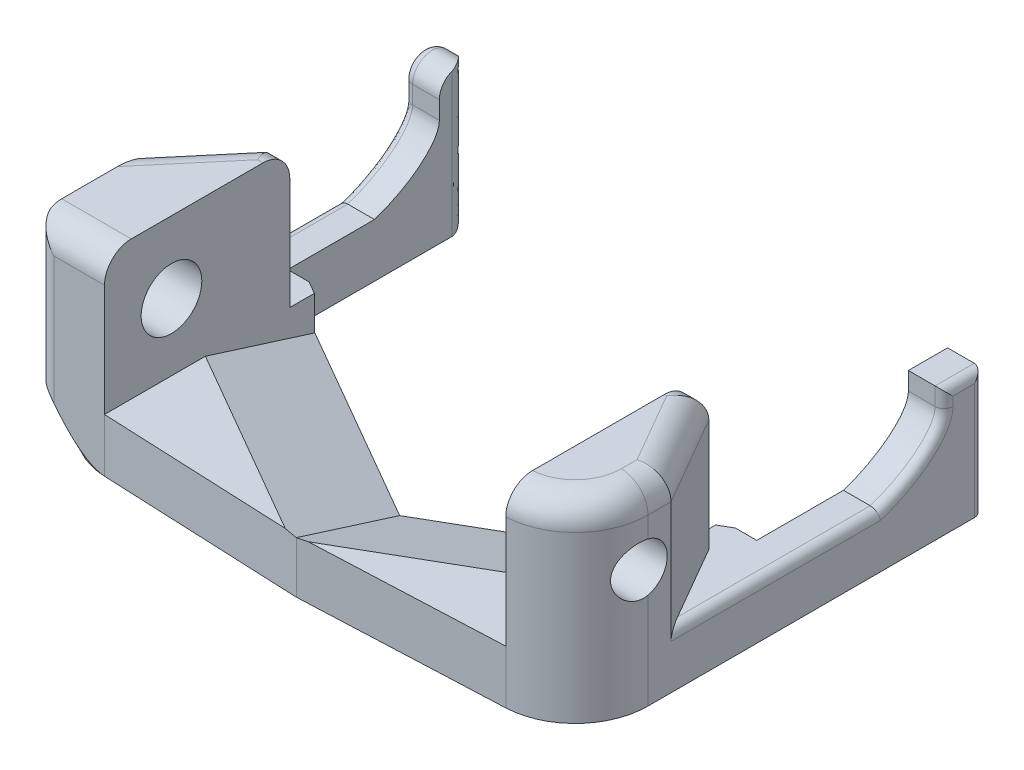
SolidWorks part; units mm, degrees
ref_plane "Front Plane" through (0, 0, 0) normal (0, 0, 1) x (1, 0, 0)
ref_plane "Top Plane" through (0, 0, 0) normal (0, 1, 0) x (1, 0, 0)
ref_plane "Right Plane" through (0, 0, 0) normal (1, 0, 0) x (0, 0, -1)
sketch "Sketch1" plane through (0, 0, 0) normal (0, 1, 0) x (1, 0, 0)
  line L0 (0, 0) -> (0, -6) construction
  line L1 (-11.8978, 6.8692) -> (0, 0) construction
  line L2 (0, 0) -> (11.25, 6.4952) construction
  line L3 (-11.25, -5.5048) -> (0, -6)
  line L4 (-11.8978, 6.8692) -> (-12.95, 6.8692) construction
  line L5 (-12.95, 14.8692) -> (-15.95, 14.8692) construction
  line L6 (-12.95, 6.8692) -> (-12.95, 14.8692) construction
  line L7 (-12.95, 14.8692) -> (-12.95, 17.3692) construction
  line L8 (0, 0) -> (-11.25, 6.4952) construction
  line L9 (-13.15, 14.8692) -> (-13.15, 17.3692)
  line L10 (-13.15, 6.6692) -> (-13.15, 14.8692)
  line L11 (-11.9514, 6.6692) -> (-13.15, 6.6692)
  line L12 (-11.9514, 6.6692) -> (0, -0.2309)
  line L13 (-11.9514, 6.6692) -> (-0.1, -0.1732) construction
  line L14 (-13.15, 17.3692) -> (-15.15, 17.3692)
  line L15 (-15.15, 17.3692) -> (-15.15, -1.4294)
  line L17 (11.9514, 6.6692) -> (0, -0.2309)
  line L18 (11.9514, 6.6692) -> (13.15, 6.6692)
  line L19 (13.15, 6.6692) -> (13.15, 14.8692)
  line L20 (13.15, 14.8692) -> (13.15, 17.3692)
  line L21 (13.15, 17.3692) -> (15.15, 17.3692)
  line L22 (15.15, 17.3692) -> (15.15, -1.4294)
  line L23 (11.25, -5.5048) -> (0, -6)
  arc A0 (-15.15, -1.4294) -> (-11.25, -5.5048) centre (-11.0706, -1.4294) ccw
  arc A1 (15.15, -1.4294) -> (11.25, -5.5048) centre (11.0706, -1.4294) cw
  dimension "D1" = 2.5
  dimension "D3" = 2
  dimension "D2" = 0.2
extrude "Boss-Extrude1" add sketch "Sketch1" against normal blind 1 contours L15 A0 L3 L23 A1 L22 L21 L20 L19 L18 L17 L12 L11 L10 L9 L14
sketch "Sketch2" plane through (0, 0, 0) normal (0, 1, 0) x (1, 0, 0)
  line L0 (-11.25, 6.2643) -> (-11.25, 0.1502)
  line L1 (-11.9514, 6.6692) -> (0, -0.2309) construction
  line L4 (-0.6469, -5.9715) -> (0, -6)
  line L11 (0, -0.2309) -> (-11.25, 6.2643)
  line L13 (-11.25, 6.4952) -> (-11.25, 0.1502) construction
  line L15 (0, -0.2309) -> (0, -6)
  line L17 (-0.6469, -5.9715) -> (-11.25, 0.1502)
sketch "Sketch3" plane through (0, 0, 0) normal (-0.171, -0.9397, 0.2962) x (0.9853, -0.1631, 0.0514)
  line L0 (0, 6.291) -> (-0.6566, 6.2965)
  line L1 (-0.6566, 6.2965) -> (-11.4182, 0.458)
  line L2 (-11.4182, 0.458) -> (-11.4182, -5.9809)
  line L3 (-11.4182, -6.1947) -> (-11.4182, 0.458) construction
  line L4 (-11.4182, -5.9809) -> (0, 0.2138)
  line L5 (0, 6.291) -> (0, 0) construction
  line L6 (0, 0.2138) -> (0, 6.291)
  line L7 (-12.1182, -6.3607) -> (0.0119, 0.2203) construction
loft "Loft1" add profiles "Sketch2", "Sketch3"
sketch "Sketch4" plane through (0, 0, 0) normal (0, 1, 0) x (1, 0, 0)
  line L0 (0, -0.2309) -> (0, -6)
  line L1 (0, -6) -> (0.6469, -5.9715)
  line L2 (11.25, -5.5048) -> (0, -6) construction
  line L3 (0.6469, -5.9715) -> (11.25, 0.1502)
  line L4 (11.25, 0.1502) -> (11.25, 6.2643)
  line L5 (11.9514, 6.6692) -> (0, -0.2309) construction
  line L6 (11.25, 6.2643) -> (0, -0.2309)
  line L7 (11.25, 0.1502) -> (11.25, 6.4952) construction
  line L8 (0.6469, -5.9715) -> (11.25, 0.1502) construction
sketch "Sketch5" plane through (0, 0, 0) normal (0.171, -0.9397, 0.2962) x (0.9853, 0.1631, -0.0514)
  line L0 (0, 0.2138) -> (0, 6.291)
  line L1 (0, 6.291) -> (0.6566, 6.2965)
  line L2 (0.6566, 6.2965) -> (11.4182, 0.458)
  line L4 (11.4182, 0.458) -> (11.4182, -5.9809)
  line L5 (11.4182, 0.458) -> (11.4182, -6.1947) construction
  line L6 (11.4182, -5.9809) -> (0, 0.2138)
  line L8 (11.4063, -5.9745) -> (-0.0119, 0.2203) construction
loft "Loft2" add profiles "Sketch4", "Sketch5"
sketch "Sketch6" plane through (0, 0, 0) normal (0, 1, 0) x (1, 0, 0)
  line L0 (-0.6469, -5.9715) -> (-11.25, 0.1502)
  line L1 (-11.25, 0.1502) -> (-11.25, -5.5048)
  line L2 (-11.25, -5.5048) -> (-0.6469, -5.9715)
sketch "Sketch7" plane through (0, 2, 0) normal (0, -1, 0) x (1, 0, 0)
  line L0 (-0.6469, 5.9715) -> (-11.25, 5.5048)
  line L1 (-11.25, 5.5048) -> (-11.25, -0.1502)
  line L2 (-11.25, -0.1502) -> (-0.6469, 5.9715)
loft "Loft3" add profiles "Sketch6", "Sketch7"
sketch "Sketch8" plane through (0, 0, 0) normal (0, 1, 0) x (1, 0, 0)
  line L0 (0.6469, -5.9715) -> (11.25, -5.5048)
  line L1 (11.25, -5.5048) -> (11.25, 0.1502)
  line L2 (11.25, 0.1502) -> (0.6469, -5.9715)
  point P7 (0.6469, -5.9616)
sketch "Sketch9" plane through (0, 2, 0) normal (0, -1, 0) x (1, 0, 0)
  line L0 (0.6469, 5.9715) -> (11.25, 5.5048)
  line L1 (11.25, 5.5048) -> (11.25, -0.1502)
  line L2 (11.25, -0.1502) -> (0.6469, 5.9715)
loft "Loft4" add profiles "Sketch8", "Sketch9"
sketch "Sketch11" plane through (0, 0, 0) normal (0, 1, 0) x (1, 0, 0)
  line L0 (11.25, 6.2643) -> (11.9514, 6.6692)
  line L1 (11.9514, 6.6692) -> (13.15, 6.6692)
  line L2 (13.15, 6.6692) -> (13.15, 17.3692)
  line L3 (13.15, 17.3692) -> (15.15, 17.3692)
  line L4 (15.15, 17.3692) -> (15.15, -1.4294)
  line L5 (11.25, 6.2643) -> (11.25, -5.5048)
  line L6 (0, -0.2039) -> (0, -6) construction
  line L7 (-11.25, 6.2643) -> (-11.25, -5.5048)
  line L8 (-15.15, 17.3692) -> (-15.15, -1.4294)
  line L9 (-13.15, 17.3692) -> (-15.15, 17.3692)
  line L10 (-13.15, 6.6692) -> (-13.15, 17.3692)
  line L11 (-11.9514, 6.6692) -> (-13.15, 6.6692)
  line L12 (-11.25, 6.2643) -> (-11.9514, 6.6692)
  arc A0 (15.15, -1.4294) -> (11.25, -5.5048) centre (11.0706, -1.4294) cw
  arc A1 (-15.15, -1.4294) -> (-11.25, -5.5048) centre (-11.0706, -1.4294) ccw
extrude "Boss-Extrude2" add sketch "Sketch11" along normal up to surface (2 mm away)
sketch "Sketch12" plane through (0, 2, 0) normal (0, 1, 0) x (1, 0, 0)
  line L0 (11.25, 4.8835) -> (12.25, 4.8835)
  line L1 (11.25, 0.1502) -> (11.25, 6.2643) construction
  line L2 (12.25, 4.8835) -> (15.15, -0.1394)
  line L3 (15.15, 17.3692) -> (15.15, -1.4294) construction
  line L4 (15.15, -0.1394) -> (15.15, -1.4294)
  line L5 (11.25, -5.5048) -> (11.25, 4.8835)
  line L6 (12.25, 4.8835) -> (12.5098, 5.0335) construction
  line L7 (12.8769, 4.3978) -> (11.45, 6.8692) construction
  line L8 (0, -0.2039) -> (0, -6) construction
  line L9 (-11.25, -5.5048) -> (-11.25, 4.8835)
  line L10 (-15.15, 1.45) -> (-15.15, -4.45)
  line L11 (-12.25, 4.8835) -> (-15.15, 1.45)
  line L12 (-11.25, 4.8835) -> (-12.25, 4.8835)
  line L13 (-15.15, -1.4294) -> (-15.15, 17.3692) construction
  line L14 (-11.25, -5.5048) -> (-14.0952, -5.5048)
  arc A0 (15.15, -1.4294) -> (11.25, -5.5048) centre (11.0706, -1.4294) cw
  arc A2 (-14.0952, -5.5048) -> (-15.15, -4.45) centre (-14.0952, -4.45) cw
  point P18 (-15.15, -4.4098)
  point P28 (-11.3233, -5.5009)
  dimension "D1" = 0.3
  dimension "D2" = 1
  dimension "D3" = 1.5
  dimension "D4" = 1
extrude "Boss-Extrude3" add sketch "Sketch12" along normal up to vertex (7.7765 mm away)
chamfer "Chamfer1" distance 3 angle 25 1 edges
sketch "Sketch15" plane through (-15.15, 0, 0) normal (-1, 0, 0) x (0, 0, 1)
  line L0 (-17.3692, 2) -> (-17.3692, 6)
  line L3 (-1.45, 2) -> (-17.3692, 2) construction
  line L4 (-15.1692, 5) -> (-15.1692, 13.2118)
  line L5 (-15.1692, 5) -> (-15.1692, 6)
  line L6 (-17.3692, 2) -> (-11.5321, 2)
  arc A0 (-17.3692, 6) -> (-15.1692, 6) centre (-16.2692, 6) cw
  spline S2 degree 3 poles (367.2976, 3980.0467) (-159.92, 375.1746) (23.9992, -4.3371) (-10.7642, 1.7947) (-11.0289, 1.8514) (-11.3061, 1.9293) (-11.4524, 1.9747) (-11.4629, 1.978) (-11.7199, 2.0588) (-12.1972, 2.2345) (-12.6635, 2.4564) (-12.9013, 2.5824) (-12.9151, 2.5898) (-13.1857, 2.7351) (-13.5424, 2.9502) (-13.9603, 3.2532) (-14.1499, 3.409) (-14.2436, 3.4911) (-14.2482, 3.4951) (-14.37, 3.6026) (-14.5274, 3.7548) (-14.7051, 3.9563) (-14.7832, 4.0563) (-14.8212, 4.1082) (-14.8226, 4.1101) (-14.9324, 4.2614) (-15.0167, 4.4063) (-19.4044, 15.2832) (110.5058, 42.3697) (3883.0831, -886.2187) knots -16.105172 -16.105172 -16.105172 -16.105172 0.125 0.125 0.1875 0.246094 0.246094 0.25 0.25 0.375 0.492187 0.492187 0.5 0.5 0.625 0.6875 0.746094 0.746094 0.75 0.75 0.8125 0.84375 0.873047 0.873047 0.875 0.875 0.9375 0.9375 5.506982 5.506982 5.506982 5.506982 only from (-9.8692, 1.7) to (-15.1692, 5)
  spline S3 degree 3 poles (-11.5321, 2) (-11.7604, 2.0738) (-12.217, 2.2439) (-12.6635, 2.4564) (-12.9013, 2.5824) (-12.9151, 2.5898) (-13.1857, 2.7351) (-13.5424, 2.9502) (-13.9603, 3.2532) (-14.1499, 3.409) (-14.2436, 3.4911) (-14.2482, 3.4951) (-14.37, 3.6026) (-14.5274, 3.7548) (-14.7051, 3.9563) (-14.7832, 4.0563) (-14.8212, 4.1082) (-14.8226, 4.1101) (-14.9324, 4.2614) (-15.0167, 4.4063) (-15.1351, 4.6998) (-15.1692, 4.8496) (-15.1692, 5) knots 0.26028 0.26028 0.26028 0.26028 0.375 0.492187 0.492187 0.5 0.5 0.625 0.6875 0.746094 0.746094 0.75 0.75 0.8125 0.84375 0.873047 0.873047 0.875 0.875 0.9375 0.9375 1 1 1 1
  dimension "D2" = 1
extrude "Boss-Extrude4" add sketch "Sketch15" against normal up to surface (2 mm away) up to face at (-13.15, 0.5, -12.0192)
sketch "Sketch16" plane through (15.15, 0, 0.3971) normal (-1, 0, 0) x (0, 0, 1)
  line L0 (-17.7662, 2) -> (-17.7662, 6)
  line L2 (-17.7662, 6) -> (-15.5662, 6)
  line L4 (-15.5662, 7.0453) -> (-15.5662, 5)
  line L6 (-17.7662, 2) -> (-11.9292, 2)
  line L7 (-15.5662, 6) -> (-15.5662, 5)
  spline S2 degree 3 poles (3882.6009, -887.4233) (110.1077, 42.3623) (-19.7973, 15.2821) (-15.4436, 4.4801) (-15.4077, 4.4073) (-15.3347, 4.2799) (-15.2915, 4.2116) (-15.2433, 4.143) (-15.2302, 4.1247) (-15.226, 4.1188) (-15.1484, 4.0118) (-14.9993, 3.8323) (-14.8011, 3.6357) (-14.6966, 3.5408) (-14.6683, 3.5155) (-14.6599, 3.508) (-14.4675, 3.338) (-14.1107, 3.0622) (-13.6578, 2.7806) (-13.4238, 2.6503) (-13.3606, 2.6158) (-13.3437, 2.6067) (-13.0913, 2.4711) (-12.6178, 2.244) (-12.1329, 2.0646) (-11.8838, 1.9855) (-11.8774, 1.9835) (29.4039, -10.9957) (-199.0711, 413.6868) (932.8156, 3879.3805) knots -4.510691 -4.510691 -4.510691 -4.510691 0.0625 0.0625 0.09375 0.09375 0.117188 0.123047 0.123047 0.125 0.125 0.1875 0.234375 0.246094 0.246094 0.25 0.25 0.375 0.46875 0.492188 0.492188 0.5 0.5 0.625 0.746094 0.746094 0.75 0.75 18.327221 18.327221 18.327221 18.327221 only from (-15.5662, 5) to (-10.2662, 1.7)
  spline S3 degree 3 poles (-15.5662, 5) (-15.5662, 4.8498) (-15.5322, 4.7001) (-15.4436, 4.4801) (-15.4077, 4.4073) (-15.3347, 4.2799) (-15.2915, 4.2116) (-15.2433, 4.143) (-15.2302, 4.1247) (-15.226, 4.1188) (-15.1484, 4.0118) (-14.9993, 3.8323) (-14.8011, 3.6357) (-14.6966, 3.5408) (-14.6683, 3.5155) (-14.6599, 3.508) (-14.4675, 3.338) (-14.1107, 3.0622) (-13.6578, 2.7806) (-13.4238, 2.6503) (-13.3606, 2.6158) (-13.3437, 2.6067) (-13.0913, 2.4711) (-12.6299, 2.2498) (-12.1577, 2.0738) (-11.9292, 2) knots 0 0 0 0 0.0625 0.0625 0.09375 0.09375 0.117188 0.123047 0.123047 0.125 0.125 0.1875 0.234375 0.246094 0.246094 0.25 0.25 0.375 0.46875 0.492188 0.492188 0.5 0.5 0.625 0.739809 0.739809 0.739809 0.739809
  dimension "D2" = 1
extrude "Boss-Extrude5" add sketch "Sketch16" along normal up to surface (2 mm away) up to face at (13.15, 0.5, -12.0192)
sketch "Sketch17" plane through (-11.25, 0, 0) normal (1, 0, 0) x (0, 0, -1)
  circle A0 centre (-1.75, 5.7548) radius 1.7
  circle A1 centre (-1.75, 5.7548) radius 1.7 construction
extrude "Cut-Extrude1" cut sketch "Sketch17" against normal up to next
sketch "Sketch18" plane through (11.25, 0, 0) normal (-1, 0, 0) x (0, 0, 1)
  circle A0 centre (1.75, 5.7548) radius 1.4
  circle A1 centre (1.75, 5.7548) radius 1.7 construction
  dimension "D1" = 2.8
extrude "Cut-Extrude2" cut sketch "Sketch18" against normal up to next
fillet "Fillet2" radius 1.5 7 edges at (15.15, 9.7765, 0.7844) (14.0179, 9.7765, 4.2498) (13.7, 9.7765, -2.3721) (11.75, 9.7765, -4.8835) (-12.6726, 9.7765, 5.5048) (-13.7, 9.7765, -3.1668) (-11.75, 9.7765, -4.8835)
fillet "Fillet3" radius 0.5 10 edges at (-15.15, 2.5, -17.3692) (-15.15, 7.1, -16.2692) (15.15, 6, -16.2692) (15.15, 2.5, -17.3692)
fillet "Fillet4" radius 1.5 1 edges at (-13.15, 2.5, -17.3692)
equation "\"Tolerance\"=0.2"
equation "\"D2@Sketch1\"=\"Tolerance\""
equation "\"D1@Sketch12\"=1.5 * \"Tolerance\""
equation "\"D1@Sketch15\"=1.5 * \"Tolerance\""
equation "\"D1@Sketch16\"=1.5 * \"Tolerance\""
